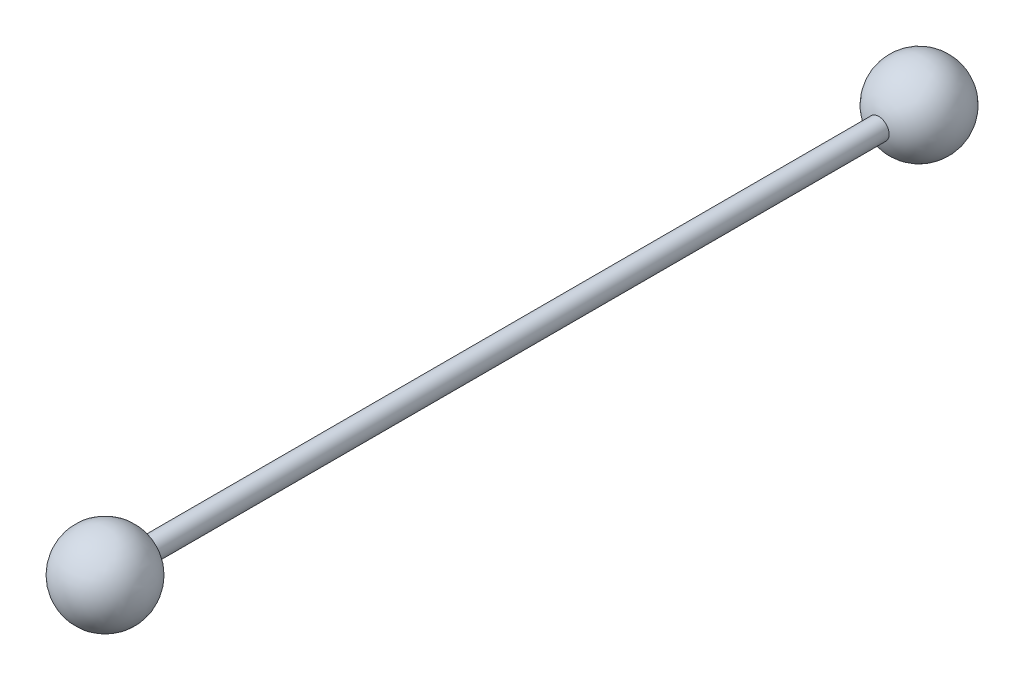
SolidWorks part; units mm, degrees
ref_plane "Front Plane" through (0, 0, 0) normal (0, 0, 1) x (1, 0, 0)
ref_plane "Top Plane" through (0, 0, 0) normal (0, 1, 0) x (1, 0, 0)
ref_plane "Right Plane" through (0, 0, 0) normal (1, 0, 0) x (0, 0, -1)
sketch "Sketch4" plane through (0, 0, 0) normal (0, 0, 1) x (1, 0, 0)
  line L0 (-3.0464, 14.6358) -> (-3.0464, -25.3642) construction
  line L1 (-3.0464, 14.6358) -> (-3.0464, 10.6358)
  line L2 (-3.0464, -25.3642) -> (-3.0464, -21.3642)
  arc A0 (-3.0464, 14.6358) -> (-3.0464, -25.3642) centre (-3.0464, -5.3642) cw
  arc A1 (-3.0464, -21.3642) -> (-3.0464, 10.6358) centre (-3.0464, -5.3642) ccw
  dimension "D4" = 16
  dimension "D5" = 20
  dimension "D1" = 40
  dimension "D2" = 4
  dimension "D3" = 4
revolve "Revolve1" add sketch "Sketch4" angle 360 about L0
ref_plane "Plane2" through (0, 0, 20) normal (0, 0, 1) x (1, 0, 0)
sketch "Sketch5" plane through (0, 0, 20) normal (0, 0, 1) x (1, 0, 0)
  circle A0 centre (-3.0464, -5.3642) radius 5
  circle A1 centre (-3.0464, -5.3642) radius 3.5
  dimension "D1" = 10
  dimension "D2" = 7
extrude "Boss-Extrude2" add sketch "Sketch5" against normal blind 4
extrude "Boss-Extrude3" add sketch "Sketch5<2>" against normal blind 4 and the other way blind 354
sketch "Sketch5<2>" plane through (0, 0, 20) normal (0, 0, 1) x (1, 0, 0) same geometry as "Sketch5"
ref_plane "Plane4" through (0, 0, 390) normal (0, 0, 1) x (1, 0, 0)
sketch "Sketch7" plane through (0, 0, 390) normal (0, 0, 1) x (1, 0, 0)
  line L0 (-3.0464, 14.6358) -> (-3.0464, -25.3642) construction
  line L1 (-3.0464, 14.6358) -> (-3.0464, 10.6358)
  line L2 (-3.0464, -25.3642) -> (-3.0464, -21.3642)
  circle A0 centre (-3.0464, -5.3642) radius 20 construction
  arc A1 (-3.0464, 10.6358) -> (-3.0464, -21.3642) centre (-3.0464, -5.3642) cw
  arc A2 (-3.0464, 14.6358) -> (-3.0464, -25.3642) centre (-3.0464, -5.3642) cw
  dimension "D1" = 4
  dimension "D2" = 4
revolve "Revolve3" add sketch "Sketch7" angle 360 about L0
